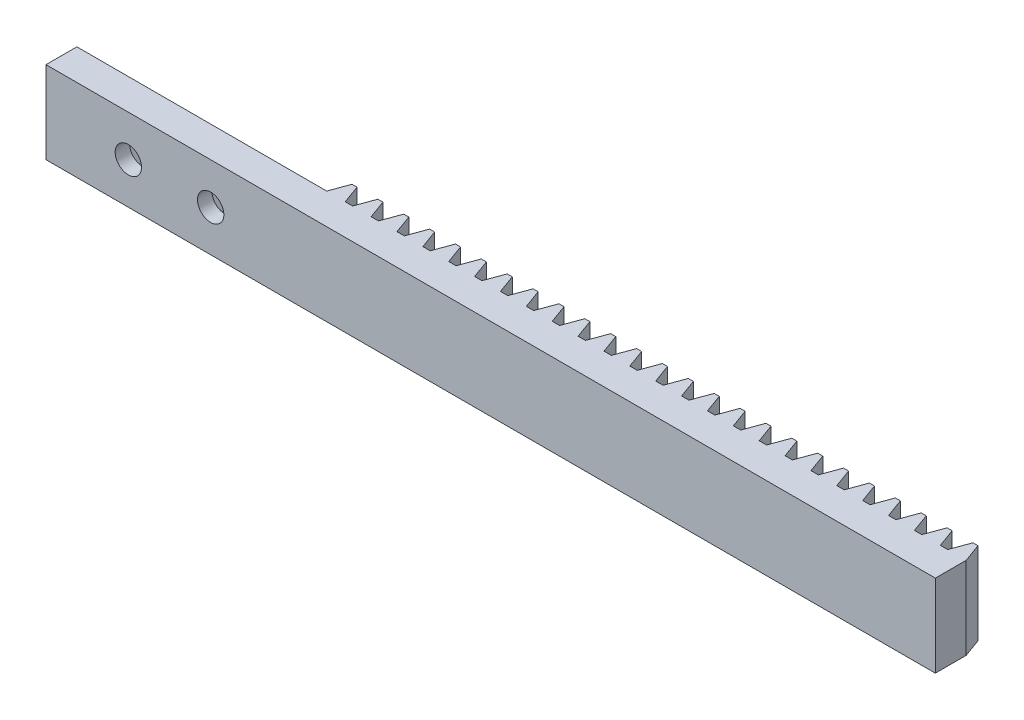
SolidWorks part; units mm, degrees
ref_plane "前视基准面" through (0, 0, 0) normal (0, 0, 1) x (1, 0, 0)
ref_plane "上视基准面" through (0, 0, 0) normal (0, 1, 0) x (1, 0, 0)
ref_plane "右视基准面" through (0, 0, 0) normal (1, 0, 0) x (0, 0, -1)
sketch "草图1" plane through (0, 0, 0) normal (0, 1, 0) x (1, 0, 0)
  line L0 (0, 0) -> (108, 0)
  line L1 (108, 0) -> (108, 3.75)
  line L2 (108, 3.75) -> (107.1812, 5.9996)
  line L3 (107.1812, 5.9996) -> (106.5662, 5.9996)
  line L4 (106.5662, 5.9996) -> (105.7474, 3.75)
  line L6 (0, 3.75) -> (108, 3.75)
  line L103 (0, 3.75) -> (0, 0)
  dimension "D1" = 108
  dimension "D2" = 3.75
  dimension "D3" = 70
  dimension "D4" = 2.394
  dimension "D5" = 0.615
  dimension "D6" = 70
extrude "凸台-拉伸1" add sketch "草图1" along normal blind 10 contours L6 L103 L0 L1 region at (54, 0, -1.875)
extrude "凸台-拉伸2" add sketch "草图1<5>" along normal blind 10 contours L4 L6 L2 L3 region at (106.8737, 0, -4.6607)
sketch "草图1<5>" plane through (0, 0, 0) normal (0, 1, 0) x (1, 0, 0) same geometry as "草图1"
pattern_linear "阵列(线性)1" count 25 spacing 3.142 along (-1, 0, 0) of "凸台-拉伸2"
sketch "草图2" plane through (0, 0, -3.75) normal (0, 0, -1) x (-1, 0, 0)
  line L0 (0, 5) -> (-12.8318, 5) construction
  line L1 (0, 10) -> (0, 0) construction
  circle A0 centre (-10, 5) radius 1.6
  circle A1 centre (-20, 5) radius 1.6
  dimension "D3" = 3.2
  dimension "D4" = 3.2
  dimension "D1" = 10
  dimension "D2" = 10
extrude "切除-拉伸1" cut sketch "草图2" against normal blind 10
sketch "草图3" plane through (0, 0, -3.75) normal (0, 0, -1) x (-1, 0, 0)
  line L1 (-21.5877, 7.75) -> (-23.1754, 5)
  line L2 (-23.1754, 5) -> (-21.5877, 2.25)
  line L3 (-21.5877, 2.25) -> (-18.4123, 2.25)
  line L4 (-18.4123, 2.25) -> (-16.8246, 5)
  line L5 (-16.8246, 5) -> (-18.4123, 7.75)
  line L6 (-18.4123, 7.75) -> (-21.5877, 7.75)
  line L7 (-11.5877, 7.75) -> (-13.1754, 5)
  line L8 (-13.1754, 5) -> (-11.5877, 2.25)
  line L9 (-11.5877, 2.25) -> (-8.4123, 2.25)
  line L10 (-8.4123, 2.25) -> (-6.8246, 5)
  line L11 (-6.8246, 5) -> (-8.4123, 7.75)
  line L12 (-8.4123, 7.75) -> (-11.5877, 7.75)
  circle A0 centre (-20, 5) radius 2.75 construction
  circle A1 centre (-10, 5) radius 2.75 construction
  dimension "D1" = 5.5
  dimension "D2" = 5.5
extrude "切除-拉伸2" cut sketch "草图3" against normal blind 2
